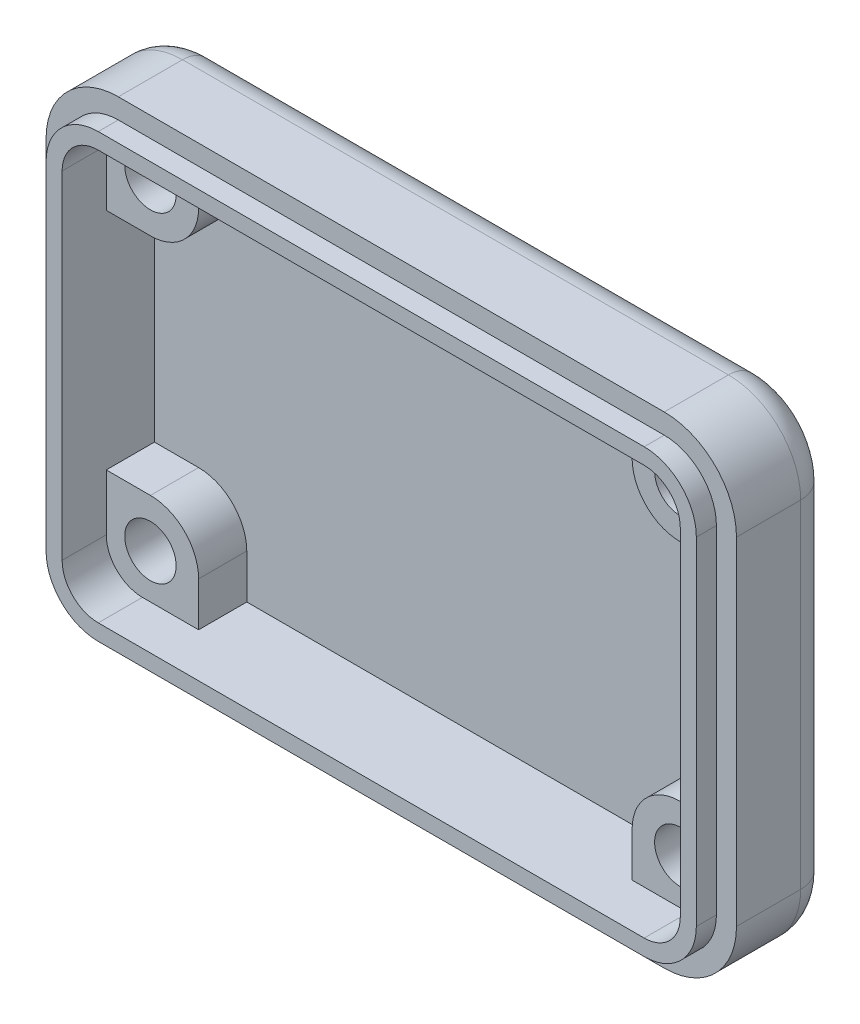
SolidWorks part; units mm, degrees
ref_plane "Front Plane" through (0, 0, 0) normal (0, 0, 1) x (1, 0, 0)
ref_plane "Top Plane" through (0, 0, 0) normal (0, 1, 0) x (1, 0, 0)
ref_plane "Right Plane" through (0, 0, 0) normal (1, 0, 0) x (0, 0, -1)
sketch "Эскиз1" plane through (0, 0, 0) normal (0, 0, 1) x (1, 0, 0)
  line L5 (-19.25, -12.75) -> (19.25, -12.75) construction
  line L6 (-19.25, -12.75) -> (-19.25, 12.75) construction
  line L7 (-19.25, 12.75) -> (19.25, 12.75) construction
  line L8 (19.25, -12.75) -> (19.25, 12.75) construction
  line L9 (-19.25, -12.75) -> (19.25, 12.75) construction
  line L10 (-19.25, 12.75) -> (19.25, -12.75) construction
  line L11 (-17, -15) -> (17, -15)
  line L12 (-21.5, -10.5) -> (-21.5, 10.5)
  line L13 (-17, 15) -> (17, 15)
  line L14 (21.5, -10.5) -> (21.5, 10.5)
  line L15 (-21.5, -15) -> (21.5, 15) construction
  line L16 (-21.5, 15) -> (21.5, -15) construction
  arc A0 (-21.5, -10.5) -> (-17, -15) centre (-17, -10.5) ccw
  arc A1 (17, -15) -> (21.5, -10.5) centre (17, -10.5) ccw
  arc A2 (21.5, 10.5) -> (17, 15) centre (17, 10.5) ccw
  arc A3 (-17, 15) -> (-21.5, 10.5) centre (-17, 10.5) ccw
  point P0 (0, 0)
  point P6 (0, 0)
  dimension "D5" = 4.5
  dimension "D1" = 38.5
  dimension "D2" = 25.5
  dimension "D3" = 2.25
  dimension "D4" = 2.25
extrude "Бобышка-Вытянуть1" add sketch "Эскиз1" along normal blind 6
sketch "Эскиз2" plane through (0, 0, 6) normal (0, 0, 1) x (1, 0, 0)
  line L0 (-21.5, 10.5) -> (-21.5, -10.5) construction
  line L1 (-17, -12.75) -> (17, -12.75)
  line L2 (-19.25, -10.5) -> (-19.25, 10.5)
  line L3 (-17, 12.75) -> (17, 12.75)
  line L4 (19.25, -10.5) -> (19.25, 10.5)
  line L5 (-19.25, -12.75) -> (19.25, 12.75) construction
  line L6 (-19.25, 12.75) -> (19.25, -12.75) construction
  line L7 (17, 15) -> (-17, 15) construction
  arc A0 (17, -12.75) -> (19.25, -10.5) centre (17, -10.5) ccw
  arc A1 (19.25, 10.5) -> (17, 12.75) centre (17, 10.5) ccw
  arc A2 (-17, 12.75) -> (-19.25, 10.5) centre (-17, 10.5) ccw
  arc A3 (-19.25, -10.5) -> (-17, -12.75) centre (-17, -10.5) ccw
  point P0 (0, 0)
  dimension "D3" = 2.25
  dimension "D1" = 2.25
  dimension "D2" = 2.25
extrude "Вырез-Вытянуть1" cut sketch "Эскиз2" against normal blind 4.5
sketch "Эскиз3" plane through (0, 0, 1.5) normal (0, 0, 1) x (1, 0, 0)
  line L0 (-13.5, 10) -> (-13.5, 13)
  line L1 (-16.5, -10) -> (16.5, -10) construction
  line L2 (-16.5, -10) -> (-16.5, 10) construction
  line L3 (-16.5, 10) -> (16.5, 10) construction
  line L4 (16.5, -10) -> (16.5, 10) construction
  line L5 (-16.5, -10) -> (16.5, 10) construction
  line L6 (-16.5, 10) -> (16.5, -10) construction
  line L8 (-13.5, 13) -> (-19.5, 13)
  line L9 (-19.5, 13) -> (-19.5, 7)
  line L11 (-19.5, 7) -> (-16.5, 7)
  line L12 (-16.5, -7) -> (-19.5, -7)
  line L14 (-19.5, -7) -> (-19.5, -13)
  line L15 (-19.5, -13) -> (-13.5, -13)
  line L16 (-13.5, -13) -> (-13.5, -10)
  line L17 (16.5, -7) -> (19.5, -7)
  line L19 (19.5, -7) -> (19.5, -13)
  line L20 (19.5, -13) -> (13.5, -13)
  line L22 (13.5, -13) -> (13.5, -10)
  line L23 (13.5, 10) -> (13.5, 13)
  line L24 (13.5, 13) -> (19.5, 13)
  line L25 (19.5, 13) -> (19.5, 7)
  line L27 (19.5, 7) -> (16.5, 7)
  arc A4 (-16.5, 7) -> (-13.5, 10) centre (-16.5, 10) ccw
  arc A5 (13.5, 10) -> (16.5, 7) centre (16.5, 10) ccw
  arc A6 (13.5, -10) -> (16.5, -7) centre (16.5, -10) cw
  arc A7 (-16.5, -7) -> (-13.5, -10) centre (-16.5, -10) cw
  point P8 (0, 0)
  dimension "D3" = 6
  dimension "D1" = 20
  dimension "D2" = 33
  dimension "D4" = 6
  dimension "D5" = 6
  dimension "D6" = 6
  dimension "D7" = 6
  dimension "D8" = 6
  dimension "D9" = 6
  dimension "D10" = 6
extrude "Бобышка-Вытянуть4" add sketch "Эскиз3" along normal blind 3
sketch "Эскиз4" plane through (0, 0, 4.5) normal (0, 0, 1) x (1, 0, 0)
  circle A0 centre (16.5, -10) radius 1.6
  circle A1 centre (-16.5, -10) radius 1.6
  circle A2 centre (-16.5, 10) radius 1.6
  circle A3 centre (16.5, 10) radius 1.6
extrude "Вырез-Вытянуть2" cut sketch "Эскиз4" against normal blind 6
sketch "Эскиз5" plane through (0, 0, 6) normal (0, 0, 1) x (1, 0, 0)
  line L1 (17, -12.75) -> (-17, -12.75)
  line L2 (19.25, -10.5) -> (19.25, 10.5)
  line L3 (17, 12.75) -> (-17, 12.75)
  line L4 (-19.25, -10.5) -> (-19.25, 10.5)
  line L5 (19.25, -12.75) -> (-19.25, 12.75) construction
  line L6 (19.25, 12.75) -> (-19.25, -12.75) construction
  line L7 (17, -13.75) -> (-17, -13.75)
  line L8 (20.25, -10.5) -> (20.25, 10.5)
  line L9 (17, 13.75) -> (-17, 13.75)
  line L10 (-20.25, -10.5) -> (-20.25, 10.5)
  line L11 (20.25, -13.75) -> (-20.25, 13.75) construction
  line L12 (20.25, 13.75) -> (-20.25, -13.75) construction
  arc A0 (17, 12.75) -> (19.25, 10.5) centre (17, 10.5) cw
  arc A1 (-19.25, 10.5) -> (-17, 12.75) centre (-17, 10.5) cw
  arc A2 (-19.25, -10.5) -> (-17, -12.75) centre (-17, -10.5) ccw
  arc A3 (17, -12.75) -> (19.25, -10.5) centre (17, -10.5) ccw
  arc A4 (17, 13.75) -> (20.25, 10.5) centre (17, 10.5) cw
  arc A5 (-20.25, 10.5) -> (-17, 13.75) centre (-17, 10.5) cw
  arc A6 (-20.25, -10.5) -> (-17, -13.75) centre (-17, -10.5) ccw
  arc A7 (17, -13.75) -> (20.25, -10.5) centre (17, -10.5) ccw
  point P0 (0, 0)
  point P6 (0, 0)
  dimension "D5" = 2.25
  dimension "D6" = 3.25
  dimension "D1" = 38.5
  dimension "D2" = 25.5
  dimension "D3" = 40.5
  dimension "D4" = 27.5
extrude "Бобышка-Вытянуть5" add sketch "Эскиз5" along normal blind 1.25
sketch "Эскиз6" plane through (0, 0, 0) normal (0, 0, -1) x (-1, 0, 0)
  circle A0 centre (16.5, -10) radius 3
  circle A1 centre (-16.5, -10) radius 3
  circle A2 centre (16.5, 10) radius 3
  circle A3 centre (-16.5, 10) radius 3
extrude "Вырез-Вытянуть3" cut sketch "Эскиз6" against normal blind 1
fillet "Скругление1" radius 2 8 edges at (0, -15, 0) (20.182, -13.682, 0) (21.5, 0, 0) (20.182, 13.682, 0) (0, 15, 0) (-20.182, 13.682, 0) (-21.5, 0, 0) (-20.182, -13.682, 0)
